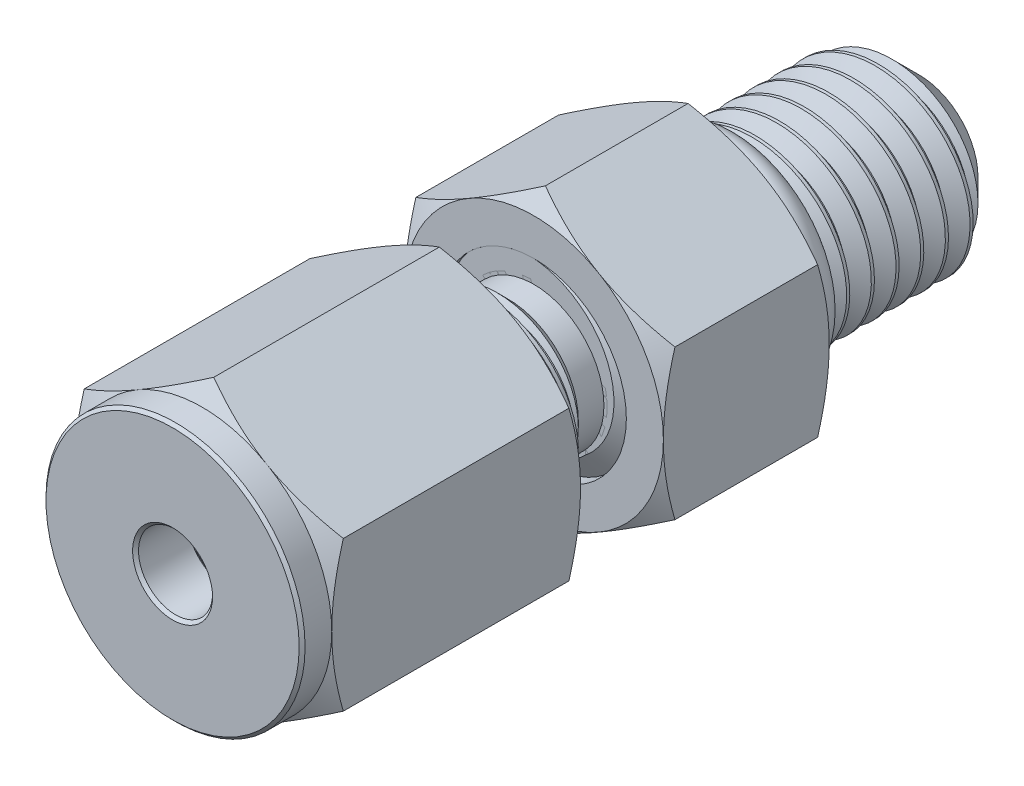
SolidWorks part; units mm, degrees
note: '?' marks a value the reader was unsure of.
ref_plane "Front Plane" through (0, 0, 0) normal (0, 0, 1) x (1, 0, 0)
ref_plane "Top Plane" through (0, 0, 0) normal (0, 1, 0) x (1, 0, 0)
ref_plane "Right Plane" through (0, 0, 0) normal (1, 0, 0) x (0, 0, -1)
sketch "Sketch1" plane through (0, 0, 0) normal (1, 0, 0) x (0, 0, -1)
  line L0 (0, 0) -> (32.004, 0) construction
  line L1 (0, 1.5875) -> (0, -1.5875) construction
  line L2 (11.938, 5.5562) -> (11.938, -5.5562) construction
  line L3 (4.7752, 3.9688) -> (4.7752, -3.9688) construction
  line L4 (4.7752, 3.9688) -> (4.7752, 2.6987) construction
  line L5 (22.606, 5.5562) -> (22.606, -5.5562) construction
  line L6 (4.2926, 3.0988) -> (9.1694, 1.9812) construction
  line L7 (9.1694, 1.9812) -> (9.1694, 1.5875) construction
  line L8 (9.1694, 1.5875) -> (4.9784, 1.5875) construction
  line L9 (4.9784, 1.5875) -> (4.2926, 2.2733) construction
  line L10 (4.2926, 2.2733) -> (4.2926, 3.0988) construction
  line L11 (2.3876, 3.0734) -> (3.4036, 3.0734) construction
  line L12 (3.4036, 3.0734) -> (3.4036, 2.2733) construction
  line L13 (3.4036, 2.2733) -> (4.2926, 2.2733) construction
  line L14 (22.606, 1.1811) -> (22.606, -1.1811) construction
  line L15 (4.2926, 2.2733) -> (4.2926, 1.5875) construction
  line L16 (4.9784, 1.5875) -> (2.3876, 1.5875) construction
  line L17 (2.3876, 1.5875) -> (2.3876, 3.0734) construction
  line L18 (4.2926, 1.5875) -> (4.9784, 1.5875) construction
  line L19 (0, 1.5875) -> (2.3876, 1.5875) construction
  line L20 (2.3876, 1.5875) -> (4.7752, 1.5875) construction
  line L21 (32.004, 3.9688) -> (32.004, -3.9688) construction
  line L22 (22.606, 3.9688) -> (22.606, -3.9688) construction
  line L23 (22.606, 3.9688) -> (32.004, 3.9688) construction
  line L24 (22.606, 3.9688) -> (22.606, 2.9104) construction
  line L25 (23.4188, 4.6609) -> (23.4188, 3.0353) construction
  line L26 (32.004, 3.4163) -> (32.004, -3.4163) construction
  circle A0 centre (23.4188, 3.8481) radius 0.8128 construction
  point P4 (1.27, 0)
  point P10 (4.7752, 0)
  point P12 (11.938, 0)
  point P15 (15.494, 0)
  point P16 (6.604, 0)
  point P17 (12.7, 0)
  point P40 (22.606, 0)
  dimension "R" = 9.398
sketch "Sketch2" plane through (0, 0, 0) normal (0, 0, 1) x (1, 0, 0)
  line L0 (0, 1.5875) -> (0, -1.5875) construction
  line L1 (0, 6.4158) -> (-5.5563, 3.2079)
  line L2 (-5.5563, 3.2079) -> (-5.5563, -3.2079)
  line L3 (-5.5563, -3.2079) -> (0, -6.4158)
  line L4 (0, -6.4158) -> (5.5562, -3.2079)
  line L5 (5.5562, -3.2079) -> (5.5562, 3.2079)
  line L6 (5.5562, 3.2079) -> (0, 6.4158)
  line L7 (0, 6.4158) -> (0, 0) construction
  circle A0 centre (0, 0) radius 5.5562 construction
extrude "Boss-Extrude1" add sketch "Sketch2" against normal up to vertex (11.938 mm away) up to point (0, 0, -11.938)
sketch "Sketch3" plane through (0, 0, 0) normal (1, 0, 0) x (0, 0, -1)
  line L0 (0, 6.4158) -> (0, 5.5562)
  line L1 (0, 3.2079) -> (0, 6.4158) construction
  line L2 (0, 5.5562) -> (1.27, 5.5562)
  line L3 (1.27, 5.5562) -> (1.7663, 6.4158)
  line L4 (11.938, 6.4158) -> (0, 6.4158) construction
  line L5 (1.7663, 6.4158) -> (11.4417, 6.4158)
  line L6 (11.4417, 6.4158) -> (11.938, 5.5562)
  line L7 (11.938, 5.5562) -> (11.938, 6.4158)
  line L8 (11.938, 6.4158) -> (11.938, 7.2754)
  line L9 (11.938, 7.2754) -> (0, 7.2754)
  line L10 (0, 7.2754) -> (0, 6.4158)
  line L11 (0, 1.5875) -> (0, 0)
  line L12 (0, 1.5875) -> (0, -1.5875) construction
  line L13 (0, 0) -> (11.938, 0)
  line L14 (11.938, 5.5562) -> (11.938, -5.5562) construction
  line L15 (11.938, 0) -> (11.938, 3.9688)
  line L16 (11.938, 3.9688) -> (4.7752, 3.9688)
  line L17 (4.7752, 3.9688) -> (4.7752, 2.6987) construction
  line L18 (4.7752, 2.6987) -> (2.3876, 2.6987) construction
  line L19 (2.3876, 2.6987) -> (2.3876, 1.5875)
  line L20 (2.3876, 1.5875) -> (0, 1.5875)
  line L21 (2.3876, 2.6987) -> (2.3876, 3.9688) construction
  line L22 (2.3876, 3.9688) -> (4.7752, 3.9688) construction
  line L23 (4.7752, 3.3337) -> (2.3876, 3.3337)
  line L24 (2.3876, 3.3337) -> (2.3876, 2.6987)
  line L25 (4.7752, 3.3337) -> (4.7752, 3.9688)
  dimension "D1" = 30
  dimension "D2" = 1.27
revolve "Cut-Revolve1" cut sketch "Sketch3" angle 360 about L0
chamfer "Chamfer1" distance 0.127 angle 45 3 edges at (1.5875, 0, -2.3876) (1.5875, 0, 0) (5.5562, 0, 0)
sketch "Sketch4" plane through (0, 0, 0) normal (1, 0, 0) x (0, 0, -1)
  line L1 (22.606, 0) -> (6.604, 0)
  line L2 (22.606, 0) -> (22.606, 3.9688)
  line L3 (22.606, 3.9688) -> (6.604, 3.9688)
  line L4 (6.604, 0) -> (6.604, 3.9688)
  dimension "D1" = 16.002
revolve "Revolve1" add sketch "Sketch4" angle 360 about L1
sketch "Sketch7" plane through (0, 0, -22.606) normal (0, 0, -1) x (-1, 0, 0)
  line L0 (0, 0) -> (0, 6.4158) construction
  line L1 (0, 6.4158) -> (-5.5563, 3.2079)
  line L2 (-5.5563, 3.2079) -> (-5.5563, -3.2079)
  line L3 (-5.5563, -3.2079) -> (0, -6.4158)
  line L4 (0, -6.4158) -> (5.5562, -3.2079)
  line L5 (5.5562, -3.2079) -> (5.5562, 3.2079)
  line L6 (5.5562, 3.2079) -> (0, 6.4158)
  circle A0 centre (0, 0) radius 5.5562 construction
extrude "Boss-Extrude2" add sketch "Sketch7" against normal up to vertex (7.112 mm away) separate body up to point (0, 0, -15.494)
sketch "Sketch9" plane through (0, 0, 0) normal (1, 0, 0) x (0, 0, -1)
  line L0 (4.2926, 3.0988) -> (4.2926, 2.2733)
  line L1 (4.2926, 2.2733) -> (4.9784, 1.5875)
  line L2 (4.9784, 1.5875) -> (9.1694, 1.5875)
  line L3 (9.1694, 1.5875) -> (9.1694, 1.9812)
  line L4 (9.1694, 1.9812) -> (4.2926, 3.0988)
revolve "Revolve2" add sketch "Sketch9" angle 360 about L0
sketch "Sketch10" plane through (0, 0, 0) normal (1, 0, 0) x (0, 0, -1)
  line L0 (2.3876, 3.0734) -> (3.4036, 3.0734)
  line L1 (3.4036, 3.0734) -> (3.4036, 2.2733)
  line L2 (3.4036, 2.2733) -> (4.2926, 2.2733)
  line L4 (4.2926, 2.2733) -> (4.9784, 1.5875)
  line L5 (4.9784, 1.5875) -> (2.3876, 1.5875)
  line L6 (2.3876, 1.5875) -> (2.3876, 3.0734)
revolve "Revolve3" add sketch "Sketch10" angle 360 about L0
sketch "Sketch11" plane through (0, 0, 0) normal (1, 0, 0) x (0, 0, -1)
  line L0 (22.606, 0) -> (32.004, 0)
  line L1 (32.004, 0) -> (32.004, 3.9688)
  line L2 (32.004, 3.9688) -> (22.606, 3.9688)
  line L3 (22.606, 3.9688) -> (22.606, 0)
revolve "Revolve4" add sketch "Sketch11" angle 360 about L0
sketch "Sketch15" plane through (0, 0, 0) normal (1, 0, 0) x (0, 0, -1)
  line L0 (0, 0) -> (23.4188, 0) construction
  circle A0 centre (23.4188, 3.8481) radius 0.8128 construction
  circle A1 centre (23.4188, 3.8481) radius 0.8128
  point P3 (23.4188, 4.6609)
  point P7 (23.4188, -4.6609)
revolve "Revolve5" add sketch "Sketch15" angle 360 about L0
sketch "Sketch17" plane through (0, 0, -22.606) normal (0, 0, -1) x (-1, 0, 0)
  line L1 (5.5562, 3.2079) -> (0, 6.4158) construction
  line L2 (0, 6.4158) -> (-5.5563, 3.2079) construction
  line L3 (-5.5563, 3.2079) -> (-5.5563, -3.2079) construction
  line L4 (-5.5563, -3.2079) -> (0, -6.4158) construction
  line L5 (0, -6.4158) -> (5.5562, -3.2079) construction
  line L6 (5.5562, -3.2079) -> (5.5562, 3.2079) construction
  circle A0 centre (0, 0) radius 5.5563
extrude "Cut-Extrude1" cut sketch "Sketch17" against normal through all draft 60 flip side to cut
sketch "Sketch18" plane through (0, 0, -15.494) normal (0, 0, 1) x (1, 0, 0)
  circle A0 centre (0, 0) radius 5.5563 construction
  circle A1 centre (0, 0) radius 5.5563
extrude "Cut-Extrude2" cut sketch "Sketch18" against normal through all draft 60 flip side to cut
sketch "Sketch16" plane through (0, 0, 0) normal (1, 0, 0) x (0, 0, -1)
  line L0 (32.004, 0) -> (6.604, 0)
  line L1 (0, 0) -> (32.004, 0) construction
  line L2 (6.604, 0) -> (6.604, 2.5691)
  line L3 (4.2926, 3.0988) -> (9.1694, 1.9812) construction
  line L4 (6.604, 2.5691) -> (10.8874, 1.5875)
  line L5 (10.8874, 1.5875) -> (12.7, 1.5875)
  line L6 (12.7, 1.5875) -> (12.7, 1.1811)
  line L7 (12.7, 1.1811) -> (32.004, 1.1811)
  line L8 (32.004, 3.9688) -> (32.004, -3.9688) construction
  line L9 (32.004, 1.1811) -> (32.004, 0) construction
  line L10 (9.1694, 1.5875) -> (4.9784, 1.5875) construction
  line L11 (32.004, 1.1811) -> (33.5915, 1.1811)
  line L12 (33.5915, 1.1811) -> (33.5915, 0)
  line L13 (33.5915, 0) -> (32.004, 0)
  dimension "D1" = 1.5875
revolve "Cut-Revolve5" cut sketch "Sketch16" angle 360 about L0
combine bodies "Combine3" operation type add bodies to combine 106 115 114
chamfer "Chamfer2" distance 1.4287 angle 45 1 edges at (3.9688, 0, -32.004)
sketch "Sketch5" plane through (0, 0, -6.604) normal (0, 0, -1) x (-1, 0, 0)
  circle A0 centre (0, 0) radius 3.9688 construction
  circle A1 centre (0, 0) radius 3.9688
  point P3 (0, 3.9688)
curve "Helix/Spiral1" pitch 1.27 height 17.272 radius 3.9688 centre (0, 0, -6.604) axis (0, 0, -1) start towards (0, 1, 0)
sketch "Sketch6" plane through (0, 0, 0) normal (1, 0, 0) x (0, 0, -1)
  line L0 (5.4134, 4.1062) -> (6.6834, 4.1062) construction
  line L1 (6.6834, 4.1062) -> (6.0484, 3.0064) construction
  line L2 (6.0484, 3.0064) -> (5.4134, 4.1062) construction
  line L3 (5.969, 3.1439) -> (6.1277, 3.1439) construction
  line L4 (5.4927, 3.9688) -> (6.604, 3.9688) construction
  line L5 (6.0484, 3.0064) -> (6.0484, 3.1439) construction
  line L6 (6.0484, 3.9688) -> (6.0484, 4.1062) construction
  line L7 (5.969, 3.1439) -> (5.4531, 4.0375)
  line L8 (5.4531, 4.0375) -> (6.6437, 4.0375)
  line L9 (6.6437, 4.0375) -> (6.1277, 3.1439)
  line L10 (6.1277, 3.1439) -> (5.969, 3.1439)
  point P10 (6.0484, 4.0375)
  dimension "D1" = 1.27
  dimension "D2" = 0.1588
sweep "Cut-Sweep1" cut profiles "Sketch6" path "Helix/Spiral1" align with end faces yes
sketch "Sketch8" plane through (0, 0, 0) normal (1, 0, 0) x (0, 0, -1)
  line L0 (6.604, 4.1062) -> (6.604, 3.0064)
  line L1 (6.604, 3.0064) -> (7.7039, 4.1062)
  line L2 (7.7039, 4.1062) -> (6.604, 4.1062)
  line L3 (15.494, 4.1062) -> (13.2943, 4.1062)
  line L4 (13.2943, 4.1062) -> (14.3941, 3.0064)
  line L5 (14.3941, 3.0064) -> (15.494, 3.0064)
  line L6 (15.494, 3.0064) -> (15.494, 4.1062)
  line L7 (15.494, 5.5562) -> (15.9903, 6.4158) construction
  line L8 (15.494, 6.4158) -> (15.494, 3.2079) construction
  line L9 (15.9903, 6.4158) -> (22.1097, 6.4158) construction
  line L10 (15.9903, 6.4158) -> (22.1097, 6.4158) construction
  line L11 (12.7, 1.1811) -> (22.606, 1.1811) construction
  line L12 (22.1097, 6.4158) -> (22.606, 5.5562) construction
  line L14 (22.606, 6.4158) -> (22.606, 7.2754) construction
  line L15 (22.606, 7.2754) -> (15.494, 7.2754) construction
  line L16 (15.494, 7.2754) -> (15.494, 6.4158) construction
  line L17 (15.494, 6.4158) -> (15.494, 5.5562) construction
  line L18 (6.0484, 3.0064) -> (6.604, 3.0064) construction
  line L19 (6.6834, 4.1062) -> (6.604, 4.1062) construction
  line L20 (7.7039, 4.1062) -> (13.2943, 4.1062) construction
  line L21 (14.3941, 3.0064) -> (6.604, 3.0064) construction
  line L22 (6.604, 2.5691) -> (10.8874, 1.5875) construction
  line L23 (22.606, 5.5562) -> (22.606, 6.4158) construction
  line L24 (6.604, 2.8063) -> (6.604, -3.1619) construction
  line L25 (4.2926, 3.0988) -> (9.1694, 1.9812) construction
  line L26 (22.606, 0) -> (6.604, 0) construction
  line L27 (6.604, 0) -> (6.604, 2.5691) construction
  line L28 (10.8874, 1.5875) -> (12.7, 1.5875) construction
  line L29 (12.7, 1.5875) -> (12.7, 1.1811) construction
  line L30 (22.606, 1.1811) -> (22.606, 0) construction
  line L31 (12.7, 0) -> (12.7, 1.1811) construction
  dimension "D1" = 30
revolve "Cut-Revolve2" cut sketch "Sketch8" angle 360 about L0
ref_plane "Plane2" through (0, 0, -33.274) normal (0, 0, -1) x (-1, 0, 0)
sketch "Sketch12" plane through (0, 0, -33.274) normal (0, 0, -1) x (-1, 0, 0)
  circle A0 centre (0, 0) radius 3.9688 construction
  circle A1 centre (0, 0) radius 2.54
  circle A2 centre (0, 0) radius 2.54
  point P0 (0, 3.9688)
  dimension "D1" = 0
curve "Helix/Spiral2" pitch 1.0583 height 10.4563 turns 9.88
sketch "Sketch13" plane through (0, 0, 0) normal (1, 0, 0) x (0, 0, -1)
  line L0 (33.2079, 4.0833) -> (34.2662, 4.0833) construction
  line L1 (33.2079, 4.0833) -> (33.737, 3.1668) construction
  line L2 (33.737, 3.1668) -> (34.2662, 4.0833) construction
  line L3 (33.6709, 3.2813) -> (33.8032, 3.2813) construction
  line L4 (33.274, 3.9688) -> (34.2, 3.9688) construction
  line L5 (33.737, 3.1668) -> (33.737, 3.2813) construction
  line L6 (33.737, 3.9688) -> (33.737, 4.0833) construction
  line L7 (33.737, 4.026) -> (34.2331, 4.026) construction
  line L8 (33.737, 3.1668) -> (33.737, -3.9688) construction
  line L9 (33.737, -3.9688) -> (32.6787, -3.9688) construction
  line L10 (32.6787, -3.9688) -> (31.6204, -3.9688) construction
  line L11 (31.6204, -3.9688) -> (30.562, -3.9688) construction
  line L12 (33.2079, 4.0833) -> (34.2331, 4.026)
  line L13 (34.2331, 4.026) -> (33.8032, 3.2813)
  line L14 (33.8032, 3.2813) -> (33.6709, 3.2813)
  line L15 (33.6709, 3.2813) -> (33.2079, 4.0833)
  line L16 (22.606, -3.9688) -> (30.5753, -3.9688) construction
  line L17 (30.562, -3.9688) -> (29.5037, -3.9688) construction
  line L18 (29.5037, -3.9688) -> (28.4454, -3.9688) construction
  dimension "D1" = 1.0583
  dimension "D2" = 0.1323
sweep "Cut-Sweep2" cut profiles "Sketch13" path "Helix/Spiral2" align with end faces yes
ref_plane "Plane1" through (2.7168, 2.8931, -23.744) normal (-0.7284, 0.684, 0.0407) x (-0.6633, -0.7187, 0.2085)
sketch "Sketch14" plane through (0, 0, 0) normal (1, 0, 0) x (0, 0, -1)
  line L0 (33.737, 3.1668) -> (32.004, 3.1668) construction
  line L1 (24.4391, 4.0833) -> (22.606, 4.0833)
  line L2 (32.004, 0) -> (22.606, 0) construction
  line L3 (32.004, 0) -> (32.004, 1.1811) construction
  line L4 (32.004, 1.1811) -> (22.606, 1.1811) construction
  line L5 (32.004, 3.9688) -> (32.004, -3.9688) construction
  line L6 (32.004, 3.1668) -> (31.0875, 4.0833) construction
  line L7 (31.0875, 4.0833) -> (32.004, 4.0833) construction
  line L8 (32.004, 4.0833) -> (32.004, 3.1668) construction
  line L9 (33.2079, 4.0833) -> (34.2662, 4.0833) construction
  line L10 (22.606, 0) -> (22.606, 1.1811) construction
  line L11 (22.606, 4.0833) -> (22.606, 3.1668)
  line L12 (22.606, 3.1668) -> (23.5225, 3.1668)
  line L13 (23.5225, 3.1668) -> (24.4391, 4.0833)
  line L14 (24.4391, 4.0833) -> (31.0875, 4.0833) construction
  line L15 (32.004, 3.1668) -> (23.5225, 3.1668) construction
  line L17 (22.606, 5.5562) -> (22.606, -5.5562) construction
revolve "Cut-Revolve4" cut sketch "Sketch14" angle 360 about L0
sketch "Sketch19" plane through (0, 0, 0) normal (1, 0, 0) x (0, 0, -1)
  line L5 (15.494, 4.8119) -> (15.494, 0) construction
  line L8 (15.494, 3.9688) -> (22.606, 3.9688)
  line L9 (15.494, 3.9688) -> (15.494, 3.1439)
  line L10 (15.494, 3.1439) -> (22.606, 3.1439)
  line L11 (22.606, 3.9688) -> (22.606, 3.1439)
  line L12 (22.606, 5.5562) -> (22.606, -5.5562) construction
revolve "Cut-Revolve7" cut sketch "Sketch19" angle 360 about L0
ref_axis "Center Axis 1" through (0, 0, -22.606) along (0, 0, -1)?
ref_plane "Contact Plane 1" through (0, 0, 0) normal (0, 0, 1) x (1, 0, 0)
ref_plane "Contact Plane 2" through (0, 0, -32.004) normal (0, 0, -1) x (-1, 0, 0)
equation "\"D4@Helix/Spiral1\" = \"Straight Thread Pitch@Sketch1\""
equation "\"D3@Helix/Spiral1\" = \"D4@Helix/Spiral1\" + \"D1@Sketch4\""
equation "\"D1@Sketch6\" = \"D4@Helix/Spiral1\""
equation "\"D2@Sketch6\" = \"D1@Sketch6\" / 8"
equation "\"D4@Helix/Spiral2\" = \"Thread Pitch@Sketch1\""
equation "\"D3@Helix/Spiral2\" = \"D4@Helix/Spiral2\" + \"R@Sketch1\""
equation "\"D1@Sketch13\" = \"D4@Helix/Spiral2\""
equation "\"D2@Sketch13\" = \"D1@Sketch13\" / 8"
